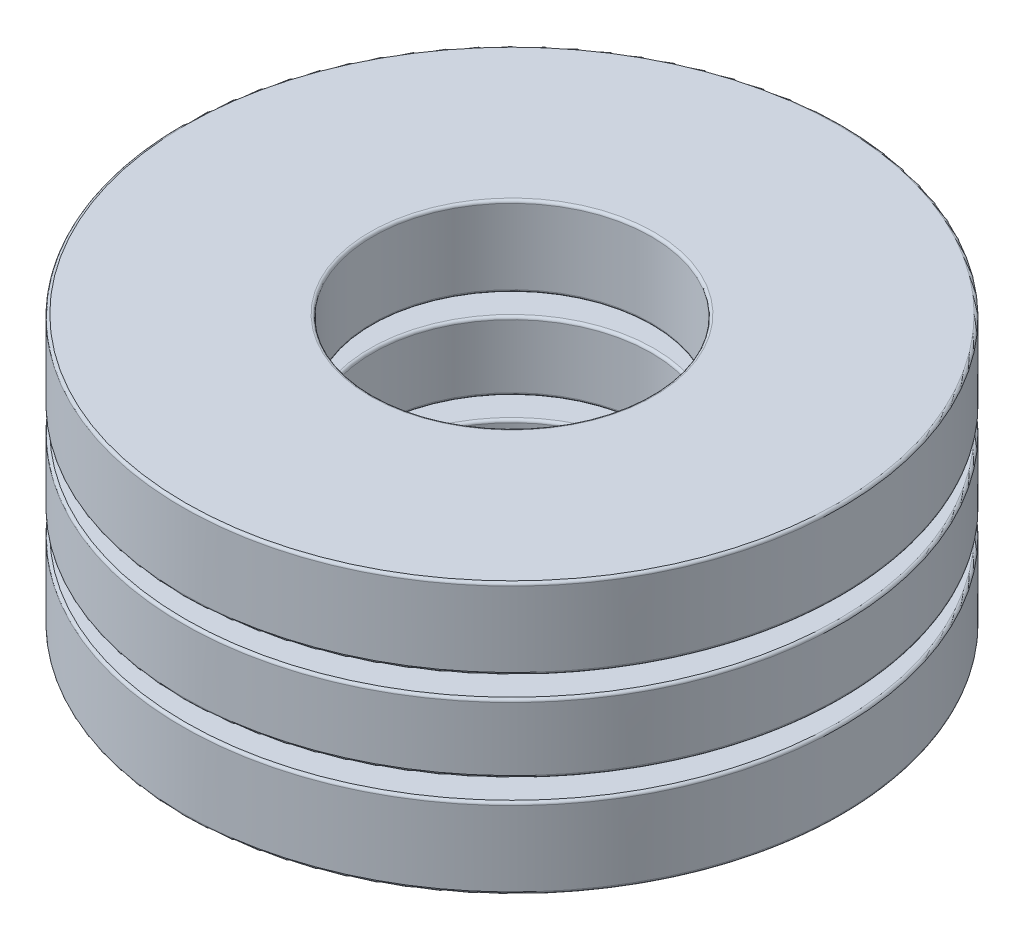
SolidWorks part; units mm, degrees
ref_plane "Front Plane" through (0, 0, 0) normal (0, 0, 1) x (1, 0, 0)
ref_plane "Top Plane" through (0, 0, 0) normal (0, 1, 0) x (1, 0, 0)
ref_plane "Right Plane" through (0, 0, 0) normal (1, 0, 0) x (0, 0, -1)
sketch "Sketch1" plane through (0, 0, 0) normal (1, 0, 0) x (0, 0, -1)
  line L0 (-6, 0) -> (6, 0) construction
  line L1 (0, -2.46) -> (0, 2.46) construction
  line L2 (-6, 0.625) -> (-2.538, 0.625)
  line L3 (-6, 0.625) -> (-6, -0.625)
  line L4 (-6, -0.625) -> (-2.538, -0.625)
  line L5 (-2.538, 0.625) -> (-2.538, -0.625)
  line L6 (-4.5, 1) -> (-4.5, -1) construction
  circle A0 centre (-4.5, 0) radius 1 construction
  dimension "D2" = 1.25
revolve "Revolve1" add sketch "Sketch1" angle 360 about L1
sketch "Sketch3" plane through (0, 0, 0) normal (1, 0, 0) x (0, 0, -1)
  line L0 (-4.5, 1.0625) -> (-4.5, -1.0625)
  line L1 (-4.5, 1) -> (-4.5, -1) construction
  line L2 (-4.4375, 1.0607) -> (-4.4375, -1.0607) construction
  arc A0 (-4.5, 1) -> (-4.5, -1) centre (-4.5, 0) ccw construction
  circle A1 centre (-4.5, 0) radius 1 construction
  arc A2 (-4.5, 1.0625) -> (-4.5, -1.0625) centre (-4.5, 0) ccw
  arc A3 (-4.4375, 1.0607) -> (-4.4375, -1.0607) centre (-4.5, 0) ccw construction
  dimension "D1" = 0.0625
revolve "Cut-Revolve1" cut sketch "Sketch3" angle 360 about L0
sketch "Sketch2" plane through (0, 0, 0) normal (1, 0, 0) x (0, 0, -1)
  line L0 (-4.5, 1) -> (-4.5, -1)
  arc A0 (-4.5, 1) -> (-4.5, -1) centre (-4.5, 0) ccw
  circle A2 centre (-4.5, 0) radius 1 construction
revolve "Revolve2" add sketch "Sketch2" angle 360 about L0
ref_axis "Axis1" through (0, 2.46, 0) along (0, -1, 0)
pattern_circular "CirPattern1" count 7 every 51.429 about axis through (0, 2.46, 0) along (0, -1, 0) of bodies 187
pattern_circular "CirPattern2" count 7 every 51.429 about axis through (0, 2.46, 0) along (0, -1, 0) of "Cut-Revolve1"
sketch "Sketch4" plane through (0, 0, 0) normal (1, 0, 0) x (0, 0, -1)
  line L0 (-6, 0.625) -> (-6, -0.625) construction
  line L1 (-6, 1) -> (-2.538, 1)
  line L2 (-6, 1) -> (-6, 2.46)
  line L3 (-6, 2.46) -> (-2.538, 2.46)
  line L4 (-2.538, 1) -> (-2.538, 2.46)
  line L5 (-6, -2.46) -> (-2.538, -2.46)
  line L6 (-6, -2.46) -> (-6, -1)
  line L7 (-6, -1) -> (-2.538, -1)
  line L8 (-2.538, -2.46) -> (-2.538, -1)
  line L10 (-2.538, 0.625) -> (-2.538, -0.625) construction
  line L11 (0, 0) -> (-6, 0) construction
  line L12 (-6, 0) -> (6, 0) construction
  dimension "Ht" = 4.92
  dimension "Washer Thickness" = 1.46
revolve "Revolve3" add sketch "Sketch4" angle 360 about L1
fillet "Fillet1" radius 0.0492 4 edges at (0, 1, -2.538) (0, 2.46, -2.538) (0, 1, -6) (0, 2.46, -6)
fillet "Fillet2" radius 0.0492 4 edges at (0, -0.625, -2.538) (0, 0.625, -2.538) (0, -0.625, -6) (0, 0.625, -6)
fillet "Fillet3" radius 0.0492 4 edges at (0, -2.46, -2.538) (0, -1, -2.538) (0, -2.46, -6) (0, -1, -6)
equation "\"D2@Sketch1\" = \"Roller Ball Dia@Sketch1\"*.625"
equation "\"Angle@CirPattern1\" = 360/\"Balls@CirPattern1\""
equation "\"D1@CirPattern2\" = \"Balls@CirPattern1\""
equation "\"D2@CirPattern2\" = \"Angle@CirPattern1\""
equation "\"D1@Fillet1\" = \"Th@Sketch1\"*.01"
equation "\"D1@Fillet2\" = \"D1@Fillet1\""
equation "\"D1@Fillet3\" = \"D1@Fillet1\""
